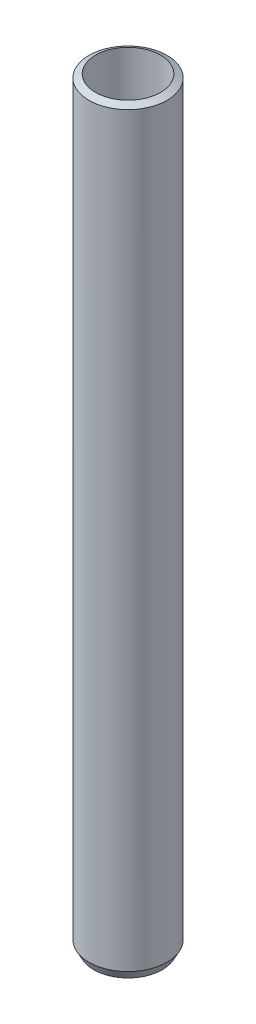
SolidWorks part; units mm, degrees
ref_plane "Front Plane" through (0, 0, 0) normal (0, 0, 1) x (1, 0, 0)
ref_plane "Top Plane" through (0, 0, 0) normal (0, 1, 0) x (1, 0, 0)
ref_plane "Right Plane" through (0, 0, 0) normal (1, 0, 0) x (0, 0, -1)
sketch "Sketch1" plane through (0, 0, 0) normal (0, 1, 0) x (1, 0, 0)
  circle A0 centre (0, 0) radius 30
  dimension "SHAFT_OD" = 60
extrude "Boss-Extrude1" add sketch "Sketch1" along normal blind 584.3259
sketch "Sketch2" plane through (0, 0, 0) normal (0, 1, 0) x (1, 0, 0)
  circle A0 centre (0, 0) radius 24.9324
  dimension "BORE_D" = 49.8648
extrude "Cut-Extrude1" cut sketch "Sketch2" along normal through all
chamfer "Chamfer1" distance 3.6542 angle 61.881 2 edges at (0, 584.3259, 30) (0, 0, 30) first distance on face at (0, 584.3259, 30) first distance on face at (0, 0, 24.9324)
